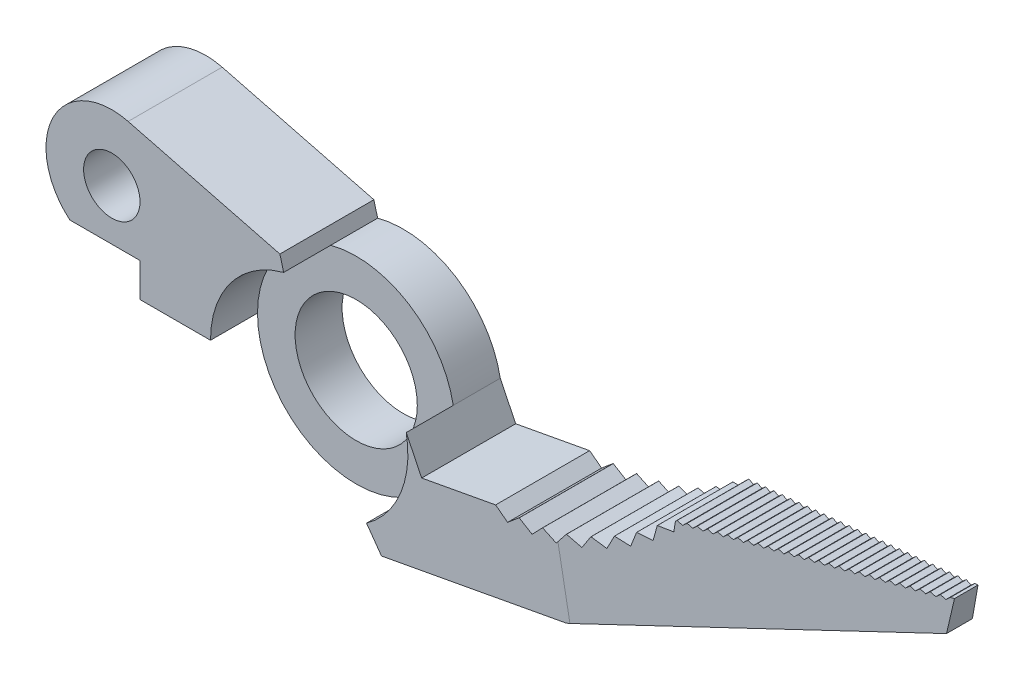
SolidWorks part; units mm, degrees
note: The reader was unsure of these and kept them because the rebuilt part matched: shared geometry of "Sketch1<3>", "Sketch1<5>".
ref_plane "Front Plane" through (0, 0, 0) normal (0, 0, 1) x (1, 0, 0)
ref_plane "Top Plane" through (0, 0, 0) normal (0, 1, 0) x (1, 0, 0)
ref_plane "Right Plane" through (0, 0, 0) normal (1, 0, 0) x (0, 0, -1)
sketch "Sketch1" plane through (0, 0, 0) normal (0, 0, 1) x (1, 0, 0)
  line L0 (-9.6304, 7.8902) -> (-1.5595, 5.82)
  line L2 (0, 0) -> (-1.5595, 5.82)
  line L3 (19.8321, 0) -> (0, 0) construction
  line L4 (0, 0) -> (0, 10.7679) construction
  line L5 (-12.7271, 1.8) -> (-9, 1.8)
  line L6 (-9, 1.8) -> (-9, 0)
  line L7 (-9, 0) -> (0, 0)
  line L8 (0, 0) -> (32.4474, 6.0138) construction
  line L9 (0, 0) -> (3.8444, -5.3897)
  line L10 (3.8444, -5.3897) -> (13.677, -3.5673)
  line L11 (13.677, -3.5673) -> (32.0857, 4.2505)
  line L12 (32.0857, 4.2505) -> (32.4474, 6.0138)
  line L13 (32.4474, 6.0138) -> (18.6818, 3.4625)
  line L14 (0, 0) -> (5.1621, 0.9567)
  line L15 (5.1621, 0.9567) -> (5.983, -0.7289)
  line L16 (5.983, -0.7289) -> (9.916, 0)
  line L17 (9.916, 0) -> (9.5867, 1.7768) construction
  circle A0 centre (0, 0) radius 5.25
  arc A1 (-9.6304, 7.8902) -> (-12.7271, 1.8) centre (-10.5, 4.5) ccw
  circle A2 centre (-10.5, 4.5) radius 1.5
  circle A3 centre (0, 0) radius 3.25
  arc A4 (9.916, 0) -> (18.6818, 3.4625) centre (10.2446, 11.9955) ccw
  dimension "D1" = 6.5
  dimension "D2" = 10.5
  dimension "D3" = 7
  dimension "D4" = 3
  dimension "D5" = 10.5
  dimension "D6" = 4.5
  dimension "D19" = 12
  dimension "D7" = 15
  dimension "D8" = 1.8
  dimension "D9" = 9
  dimension "D10" = 10.5
  dimension "D11" = 10
  dimension "D12" = 20
  dimension "D13" = 33
  dimension "D14" = 65
  dimension "D15" = 6
  dimension "D16" = 1.8
  dimension "D17" = 19
  dimension "D18" = 4
  dimension "D20" = 4.5
extrude "Boss-Extrude1" add sketch "Sketch1" along normal blind 5 contours L0 A1 L5 L6 L7 A0 L2 A2 | A4 L16 L15 A0 L9 L10 L11 L12 L13
extrude "Boss-Extrude2" add sketch "Sketch1<3>" along normal blind 2.5 contours A0
sketch "Sketch1<3>" plane through (0, 0, 0) normal (0, 0, 1) x (1, 0, 0) same geometry as "Sketch1"
extrude "Cut-Extrude4" cut sketch "Sketch1<5>" against normal through all and the other way through all contours A3
sketch "Sketch1<5>" plane through (0, 0, 0) normal (0, 0, 1) x (1, 0, 0) same geometry as "Sketch1"
sketch "Sketch2" plane through (0, 0, 0) normal (-0.1822, 0.9833, 0) x (0.9833, 0.1822, 0)
  line L0 (13, 0) -> (33, -1.875)
  line L1 (33, 0) -> (19, 0) construction
  line L2 (33, -5) -> (33, 0) construction
  line L3 (33, -1.875) -> (33, 0)
  line L4 (33, 0) -> (13, 0)
  line L5 (19, -2.5) -> (33, -2.5) construction
  line L6 (19, -5) -> (19, 0) construction
  line L7 (33, -3.125) -> (33, -5)
  line L8 (13, -5) -> (33, -3.125)
  line L9 (33, -5) -> (13, -5)
  dimension "D1" = 20
  dimension "D2" = 1.25
extrude "Cut-Extrude1" cut sketch "Sketch2" against normal through all
sketch "Sketch3" plane through (0, 0, 0) normal (0, 0, 1) x (1, 0, 0)
  line L0 (31.7591, 5.8862) -> (32.0323, 5.7843)
  line L1 (32.4474, 6.0138) -> (18.6818, 3.4625) construction
  line L2 (32.0323, 5.7843) -> (32.2508, 5.9773)
  line L3 (32.2508, 5.9773) -> (31.7591, 5.8862)
  point P6 (32.0049, 5.9318)
  dimension "D1" = 0.5
  dimension "D2" = 0.15
  dimension "D3" = 0.2
extrude "Cut-Extrude2" cut sketch "Sketch3" along normal through all and the other way through all
pattern_linear "LPattern1" count 28 spacing 0.5 along (-0.9833, -0.1822, 0) of "Cut-Extrude2"
sketch "Sketch4" plane through (0, 0, 0) normal (0, 0, 1) x (1, 0, 0)
  line L0 (9.916, 0) -> (11.1657, 0.0309)
  line L1 (9.916, 0) -> (10.5532, -0.4844)
  line L2 (10.5532, -0.4844) -> (11.1657, 0.0309)
  arc A0 (9.916, 0) -> (13.1558, 0.354) centre (10.2446, 11.9955) ccw construction
  dimension "D1" = 0.5
  dimension "D2" = 1.25
extrude "Cut-Extrude3" cut sketch "Sketch4" along normal through all
pattern_circular "CirPattern1" count 8 every 6 about axis through (10.2446, 11.9955, 0) along (0, 0, 1) of "Cut-Extrude3"
